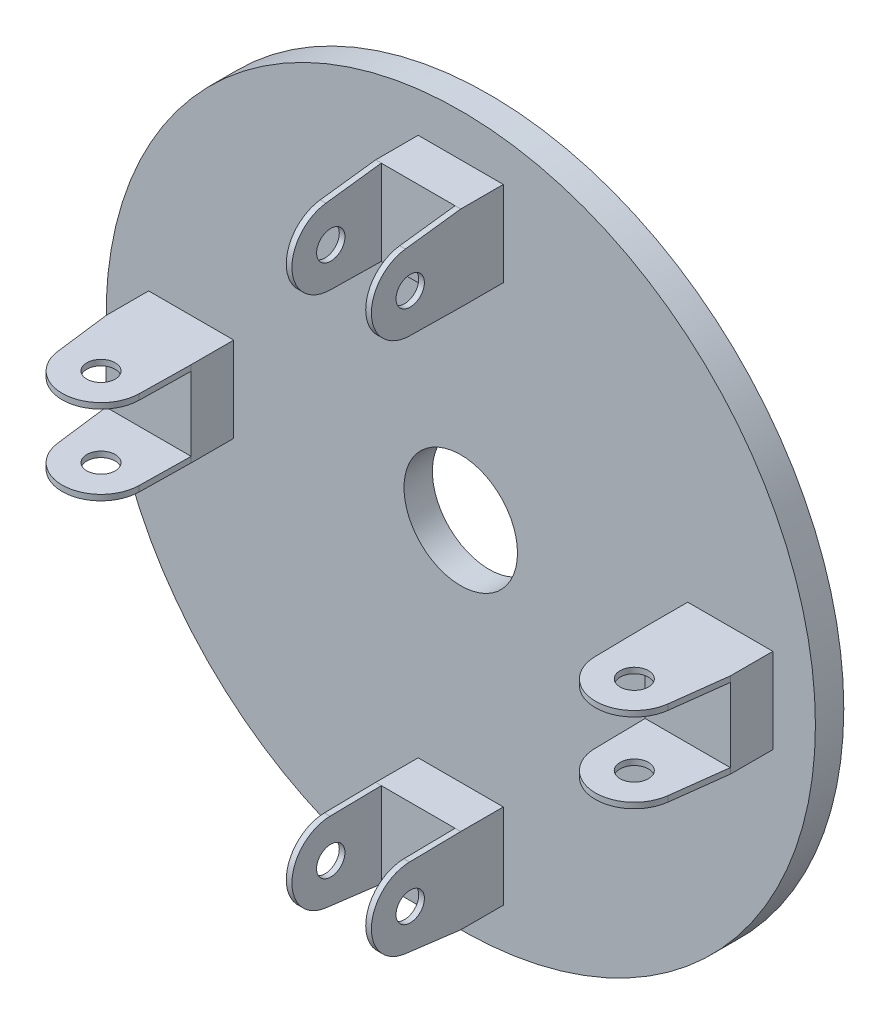
SolidWorks part; units mm, degrees
ref_plane "前视基准面" through (0, 0, 0) normal (0, 0, 1) x (1, 0, 0)
ref_plane "上视基准面" through (0, 0, 0) normal (0, 1, 0) x (1, 0, 0)
ref_plane "右视基准面" through (0, 0, 0) normal (1, 0, 0) x (0, 0, -1)
sketch "草图1" plane through (0, 0, 0) normal (0, 0, 1) x (1, 0, 0)
  line L0 (-80, -15) -> (-110, -15)
  line L1 (-15, 80) -> (15, 80)
  line L2 (-15, 80) -> (-15, 110)
  line L3 (-15, 110) -> (15, 110)
  line L4 (15, 80) -> (15, 110)
  line L5 (-15, 80) -> (15, 110) construction
  line L6 (-15, 110) -> (15, 80) construction
  line L7 (-80, 15) -> (-110, 15)
  line L8 (-110, -15) -> (-110, 15)
  line L9 (-80, -15) -> (-80, 15)
  line L10 (15, -80) -> (15, -110)
  line L11 (-15, -80) -> (-15, -110)
  line L12 (15, -110) -> (-15, -110)
  line L13 (15, -80) -> (-15, -80)
  line L14 (80, 15) -> (110, 15)
  line L15 (80, -15) -> (110, -15)
  line L16 (110, 15) -> (110, -15)
  line L17 (80, 15) -> (80, -15)
  circle A0 centre (0, 0) radius 125
  circle A1 centre (0, 0) radius 125
  circle A2 centre (0, 0) radius 125
  circle A3 centre (0, 0) radius 125
  circle A4 centre (0, 0) radius 20
  point P3 (0, 95)
  point P26 (0, 0)
  dimension "D1" = 250
  dimension "D4" = 40
  dimension "D2" = 30
  dimension "D5" = 80
  dimension "D6" = 15
  dimension "D7" = 30
  dimension "D3" = 4
extrude "凸台-拉伸1" add sketch "草图1" along normal blind 10 contours A0 A4 L4 L1 L2 L3 L9 L0 L8 L7 L13 L10 L12 L11 L17 L14 L16 L15 region at (-121.4645, 0, 0)
extrude "凸台-拉伸2" add sketch "草图1<3>" along normal blind 25 contours L0 L9 L7 L8 | L1 L4 L3 L2 | L14 L17 L15 L16 | L10 L13 L11 L12 region at (-95, 0, 0) region at (0, 95, 0) region at (0, -95, 0) region at (95, 0, 0)
sketch "草图1<3>" plane through (0, 0, 0) normal (0, 0, 1) x (1, 0, 0) same geometry as "草图1"
sketch "草图4" plane through (0, -15, 0) normal (0, -1, 0) x (1, 0, 0)
  line L0 (107.5504, 44.5109) -> (110, 25)
  line L1 (80.29, 43.0263) -> (80, 25)
  arc A0 (80.29, 43.0263) -> (107.5504, 44.5109) centre (93.9726, 42.8062) cw
  circle A1 centre (93.9726, 42.8062) radius 5
  line M3 (110, 25) -> (80, 25)
  dimension "D1" = 10
sketch "草图7" plane through (0, 15, 0) normal (0, 1, 0) x (1, 0, 0)
  line L0 (107.5504, -44.5109) -> (110, -25)
  line L1 (80.29, -43.0263) -> (80, -25)
  arc A0 (80.29, -43.0263) -> (107.5504, -44.5109) centre (93.9726, -42.8062) ccw
  arc A1 (80.29, -43.0263) -> (107.5504, -44.5109) centre (93.9726, -42.8062) ccw construction
  circle A2 centre (93.9726, -42.8062) radius 5
  line M4 (80, -25) -> (110, -25)
  dimension "D1" = 10
extrude "凸台-拉伸3" add sketch "草图7" against normal blind 2 contours L1 A0 L0 A2 M4 region at (93.2522, 15, 56.036)
extrude "凸台-拉伸4" add sketch "草图4" against normal blind 2 contours A0 L1 L0 A1 M3 region at (108.3437, -15, 34.7013)
pattern_circular "阵列(圆周)1" count 4 every 90 about axis through (0, 0, 10) along (0, 0, 1) of "凸台-拉伸3", "凸台-拉伸4"
